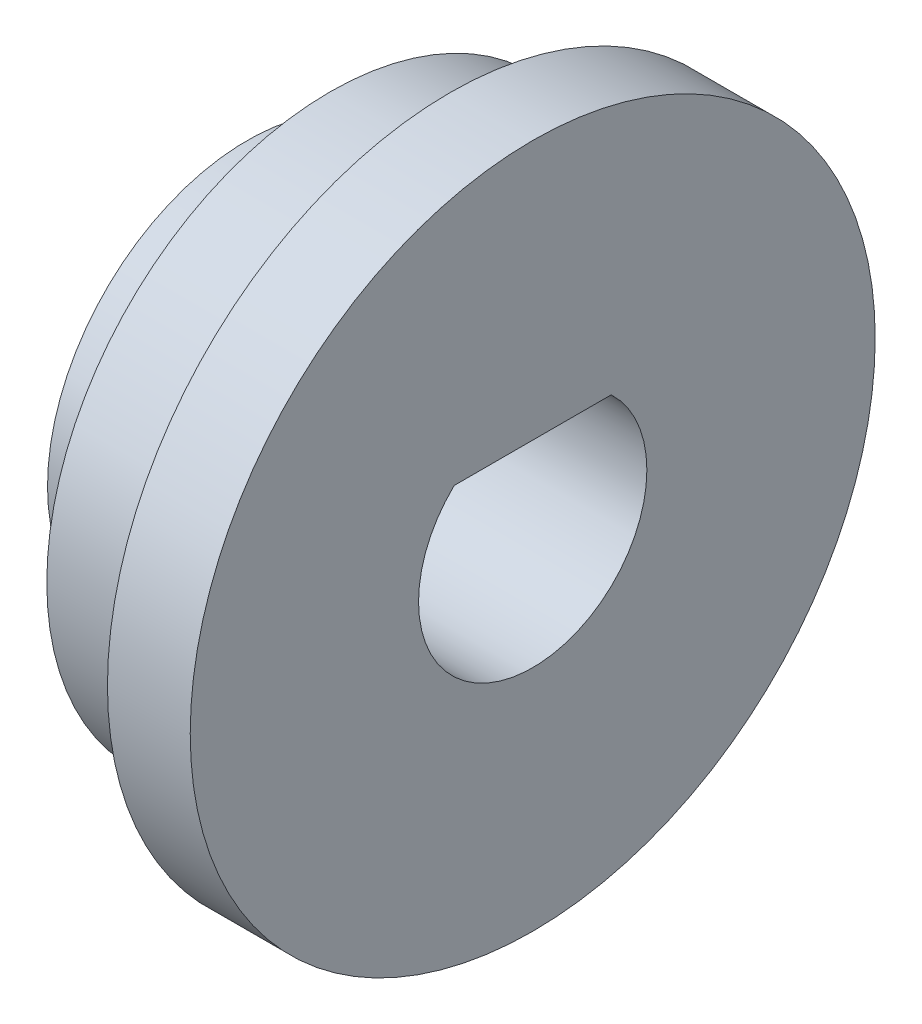
SolidWorks part; units mm, degrees
ref_plane "Ebene vorne" through (0, 0, 0) normal (0, 0, 1) x (1, 0, 0)
ref_plane "Ebene oben" through (0, 0, 0) normal (0, 1, 0) x (1, 0, 0)
ref_plane "Ebene rechts" through (0, 0, 0) normal (1, 0, 0) x (0, 0, -1)
sketch "Skizze1" plane through (0, 0, 0) normal (0, 0, 1) x (1, 0, 0)
  line L0 (0, 0) -> (-16052.284, 0) construction
  line L1 (0, 0) -> (0, 7)
  line L2 (0, 7) -> (2.9, 7)
  line L3 (2.9, 7) -> (2.9, 9.925)
  line L4 (2.9, 9.925) -> (7.1, 9.925)
  line L7 (7.1, 9.925) -> (7.1, 12)
  line L8 (7.1, 12) -> (10, 12)
  line L9 (10, 12) -> (10, 0)
  line L10 (10, 0) -> (0, 0)
  dimension "D1" = 2.9
  dimension "D2" = 24
  dimension "D3" = 4.2
  dimension "D4" = 10
  dimension "D5" = 14
  dimension "D6" = 19.85
revolve "Rotation1" add sketch "Skizze1" angle 360 about L0
sketch "Skizze2" plane through (0, 0, 0) normal (-1, 0, 0) x (0, 0, 1)
  line L0 (-2.75, 2.9047) -> (2.75, 2.9047)
  arc A0 (-2.75, 2.9047) -> (2.75, 2.9047) centre (0, 0) ccw
  dimension "D1" = 4
  dimension "D2" = 5.5
extrude "Schnitt-Linear austragen1" cut sketch "Skizze2" against normal through all
